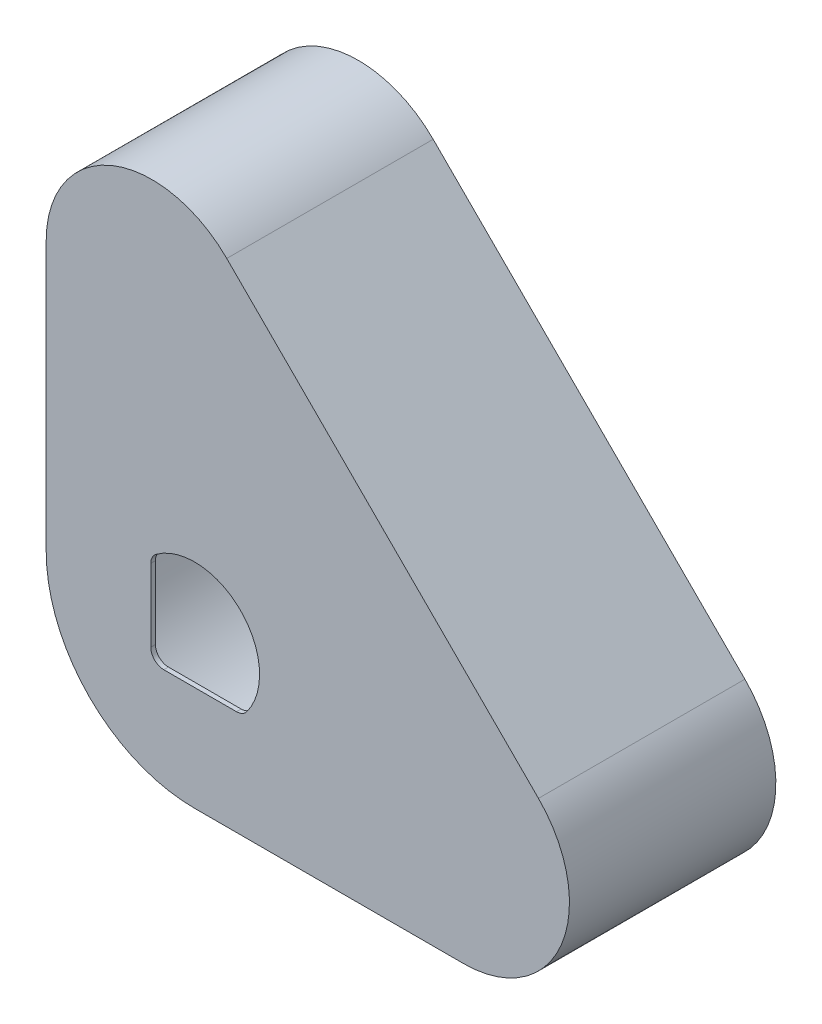
SolidWorks part; units mm, degrees
material "Nylon 101"
ref_plane "Front Plane" through (0, 0, 0) normal (0, 0, 1) x (1, 0, 0)
ref_plane "Top Plane" through (0, 0, 0) normal (0, 1, 0) x (1, 0, 0)
ref_plane "Right Plane" through (0, 0, 0) normal (1, 0, 0) x (0, 0, -1)
sketch "Sketch2" plane through (0, 0, 0) normal (0, 0, 1) x (1, 0, 0)
  line L0 (-50.8, 0) -> (-50.8, 92.075)
  line L1 (0, -50.8) -> (92.075, -50.8)
  line L2 (10.9887, 117.6687) -> (117.6687, 10.9887)
  arc A0 (-50.8, 0) -> (0, -50.8) centre (0, 0) ccw
  arc A1 (10.9887, 117.6687) -> (-50.8, 92.075) centre (-14.605, 92.075) ccw
  arc A2 (92.075, -50.8) -> (117.6687, 10.9887) centre (92.075, -14.605) ccw
  point P4 (92.1962, -25.4)
  point P7 (-25.4, 92.075)
  dimension "D1" = 101.6
  dimension "D2" = 72.39
  dimension "D3" = 92.075
  dimension "D4" = 92.075
extrude "Boss-Extrude1" add sketch "Sketch2" along normal blind 70.6437
shell "Shell2" thickness 1.5875 removed face at (20.1173, 20.1173, 0)
sketch "Sketch3" plane through (0, 0, 70.6437) normal (0, 0, 1) x (1, 0, 0)
  line L0 (-10.5604, -14.9969) -> (14.3104, -14.9969)
  line L1 (-15.0054, -10.5519) -> (-15.0054, 14.3041)
  arc A0 (17.888, -13.1898) -> (-13.2005, 17.8801) centre (0, 0) ccw
  arc A1 (-15.0054, -10.5519) -> (-10.5604, -14.9969) centre (-10.5604, -10.5519) ccw
  arc A2 (-13.2005, 17.8801) -> (-15.0054, 14.3041) centre (-10.5604, 14.3041) ccw
  arc A3 (14.3104, -14.9969) -> (17.888, -13.1898) centre (14.3104, -10.5519) ccw
  point P11 (-10.3434, -10.7647)
  dimension "D1" = 44.45
  dimension "D2" = 8.89
  dimension "D4" = 24.8559
  dimension "D5" = 24.8708
  dimension "D3" = 14.9286
  dimension "D6" = 15.0054
extrude "Cut-Extrude1" cut sketch "Sketch3" against normal through all
equation "\"D4@Sketch2\"=\"D3@Sketch2\""
